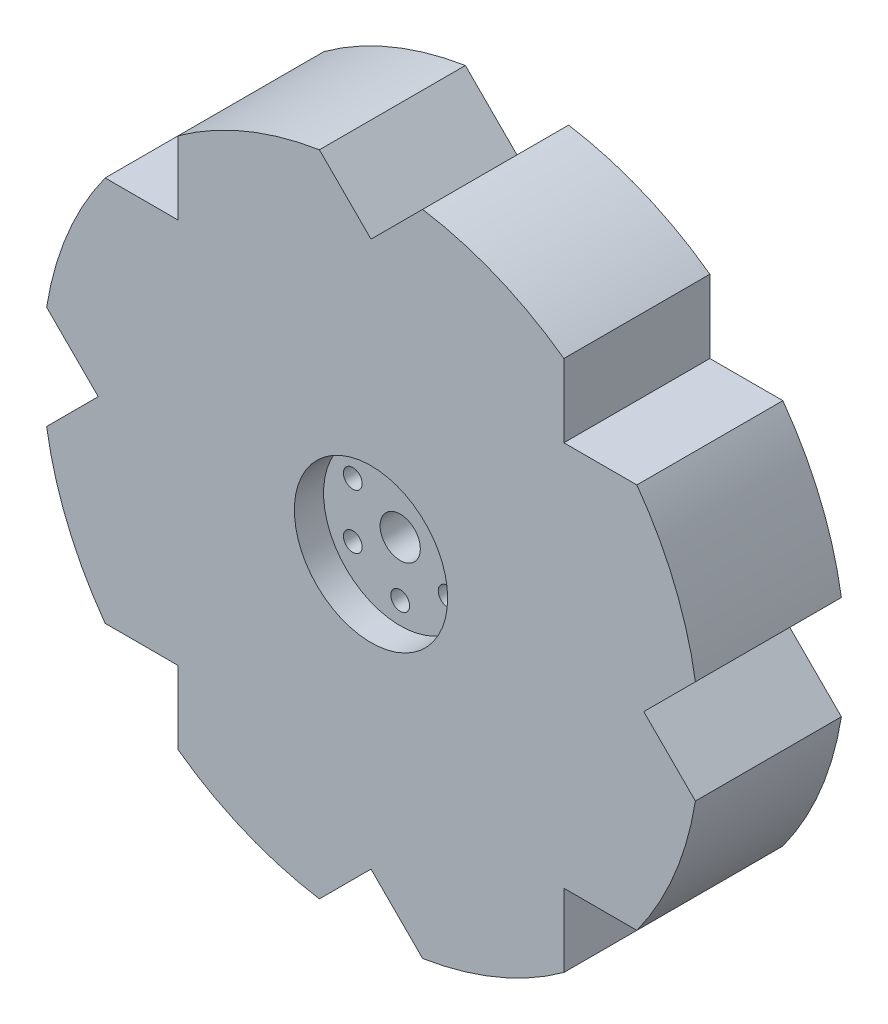
SolidWorks part; units mm, degrees
material "PE High Density Film"
ref_plane "Front Plane" through (0, 0, 0) normal (0, 0, 1) x (1, 0, 0)
ref_plane "Top Plane" through (0, 0, 0) normal (0, 1, 0) x (1, 0, 0)
ref_plane "Right Plane" through (0, 0, 0) normal (1, 0, 0) x (0, 0, -1)
sketch "Sketch1" plane through (0, 0, 0) normal (0, 0, 1) x (1, 0, 0)
  line L0 (0, 0) -> (0, 57.15) construction
  line L1 (-8.9803, 56.44) -> (0, 47.4598)
  line L2 (0, 47.4598) -> (8.9803, 56.44)
  line L3 (33.5591, 46.2591) -> (33.5591, 33.5591)
  line L4 (33.5591, 33.5591) -> (46.2591, 33.5591)
  line L5 (56.44, 8.9803) -> (47.4598, 0)
  line L6 (47.4598, 0) -> (56.44, -8.9803)
  line L7 (46.2591, -33.5591) -> (33.5591, -33.5591)
  line L8 (33.5591, -33.5591) -> (33.5591, -46.2591)
  line L9 (8.9803, -56.44) -> (0, -47.4598)
  line L10 (0, -47.4598) -> (-8.9803, -56.44)
  line L11 (-33.5591, -46.2591) -> (-33.5591, -33.5591)
  line L12 (-33.5591, -33.5591) -> (-46.2591, -33.5591)
  line L13 (-56.44, -8.9803) -> (-47.4598, 0)
  line L14 (-47.4598, 0) -> (-56.44, 8.9803)
  line L15 (-46.2591, 33.5591) -> (-33.5591, 33.5591)
  line L16 (-33.5591, 33.5591) -> (-33.5591, 46.2591)
  arc A0 (-56.44, -8.9803) -> (-46.2591, -33.5591) centre (0, 0) ccw
  arc A1 (-46.2591, 33.5591) -> (-56.44, 8.9803) centre (0, 0) ccw
  arc A2 (-33.5591, -46.2591) -> (-8.9803, -56.44) centre (0, 0) ccw
  arc A3 (8.9803, -56.44) -> (33.5591, -46.2591) centre (0, 0) ccw
  arc A4 (46.2591, -33.5591) -> (56.44, -8.9803) centre (0, 0) ccw
  arc A5 (56.44, 8.9803) -> (46.2591, 33.5591) centre (0, 0) ccw
  arc A6 (33.5591, 46.2591) -> (8.9803, 56.44) centre (0, 0) ccw
  arc A7 (-8.9803, 56.44) -> (-33.5591, 46.2591) centre (0, 0) ccw
  point P30 (0, 0)
  dimension "D1" = 114.3
  dimension "D2" = 45
  dimension "D3" = 12.7
  dimension "D4" = 8
extrude "Boss-Extrude1" add sketch "Sketch1" along normal blind 25.4
sketch "Sketch2" plane through (0, 0, 25.4) normal (0, 0, 1) x (1, 0, 0)
  circle A0 centre (0, 0) radius 3.5
  dimension "D1" = 7
extrude "Cut-Extrude1" cut sketch "Sketch2" against normal through all contours A0 region at (0, 0, 25.4)
sketch "Sketch3" plane through (0, 0, 25.4) normal (0, 0, 1) x (1, 0, 0)
  circle A0 centre (0, 0) radius 13.335
  dimension "D1" = 26.67
extrude "Cut-Extrude2" cut sketch "Sketch3" against normal blind 5.08
sketch "Sketch4" plane through (0, 0, 0) normal (0, 0, -1) x (-1, 0, 0)
  circle A0 centre (0, 0) radius 22.86
  dimension "D1" = 45.72
extrude "Cut-Extrude3" cut sketch "Sketch4" against normal blind 5.08
sketch "Sketch5" plane through (0, 0, 5.08) normal (0, 0, -1) x (-1, 0, 0)
  line L0 (0, 0) -> (0, 9.525) construction
  circle A0 centre (0, 0) radius 9.525 construction
  circle A1 centre (0, 9.525) radius 1.5875
  circle A2 centre (8.2489, 4.7625) radius 1.5875
  circle A3 centre (8.2489, -4.7625) radius 1.5875
  circle A4 centre (0, -9.525) radius 1.5875
  circle A5 centre (-8.2489, -4.7625) radius 1.5875
  circle A6 centre (-8.2489, 4.7625) radius 1.5875
  point P17 (0, 0)
  dimension "D1" = 19.05
  dimension "D2" = 3.175
  dimension "D3" = 6
hole_wizard "#4 Clearance Hole1" positions "Sketch6" profile "Sketch8" hole size "#4" standard "ANSI Inch" end condition through all
sketch "Sketch6" plane through (0, 0, 5.08) normal (0, 0, -1) x (-1, 0, 0)
  point P0 (0, 9.525)
  point P3 (8.2489, 4.7625)
  point P6 (8.2489, -4.7625)
  point P9 (0, -9.525)
  point P13 (-8.2489, 4.7625)
  point P16 (-8.2489, -4.7625)
sketch "Sketch8" plane through (0, 9.525, 5.08) normal (1, 0, 0) x (0, 1, 0)
  line L0 (0, 0) -> (0, 20.32)
  line L1 (0, 20.32) -> (1.6319, 20.32)
  line L2 (1.6319, 20.32) -> (1.6319, 0)
  line L5 (1.6319, 0) -> (0, 0)
  line L11 (0, -6.35) -> (0, 107.95) construction
  dimension "Thru Hole Dia." = 3.2639
  dimension "Thru Hole Depth" = 20.32
